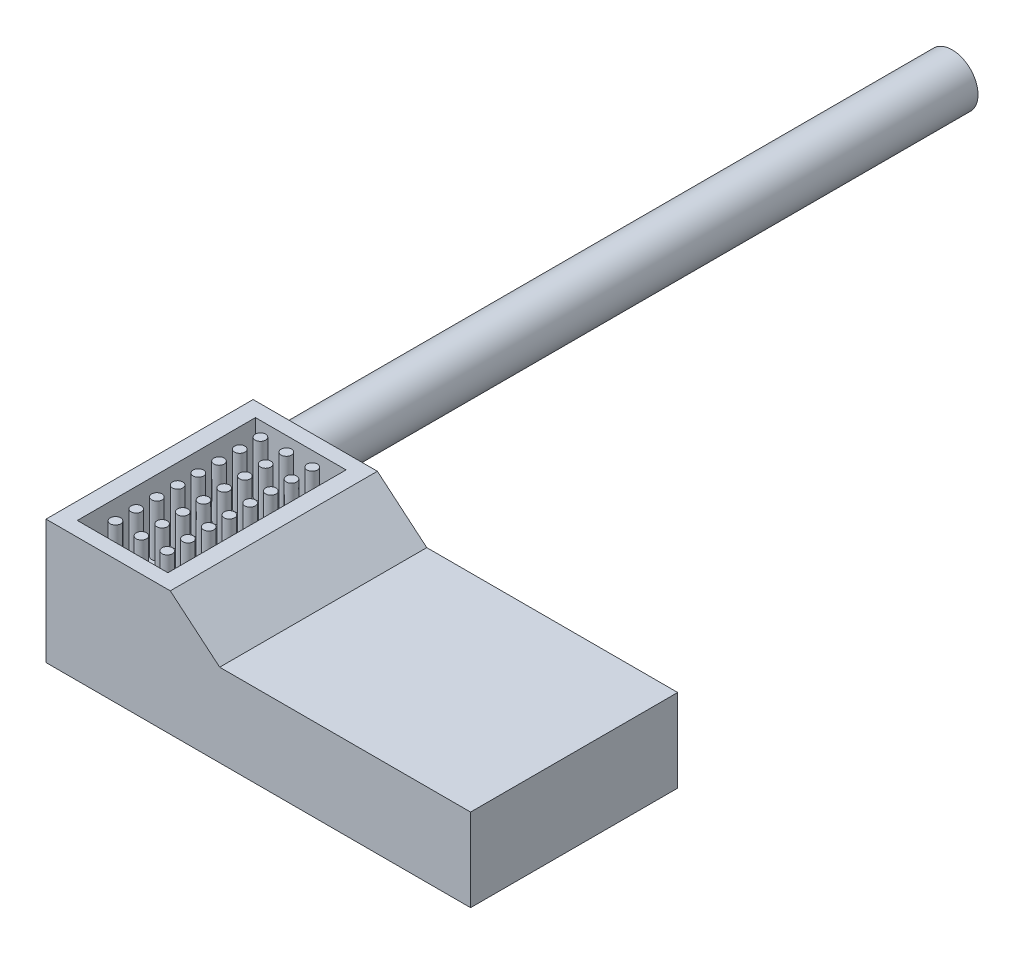
SolidWorks part; units mm, degrees
ref_plane "Front Plane" through (0, 0, 0) normal (0, 0, 1) x (1, 0, 0)
ref_plane "Top Plane" through (0, 0, 0) normal (0, 1, 0) x (1, 0, 0)
ref_plane "Right Plane" through (0, 0, 0) normal (1, 0, 0) x (0, 0, -1)
sketch "Sketch2" plane through (0, 0, 0) normal (0, 0, 1) x (1, 0, 0)
  line L0 (-3.6523, 7.7816) -> (-8.4239, 11.7816)
  line L1 (20.5761, -0.2184) -> (-20.4239, -0.2184)
  line L2 (20.5761, -0.2184) -> (20.5761, 7.7816)
  line L3 (20.5761, 7.7816) -> (-3.6523, 7.7816)
  line L4 (-20.4239, 11.7816) -> (-20.4239, -0.2184)
  line L7 (-8.4239, 11.7816) -> (-20.4239, 11.7816)
  point P0 (0, 0)
  dimension "D1" = 41
  dimension "D2" = 12
  dimension "D3" = 12
  dimension "D4" = 8
extrude "Boss-Extrude1" add sketch "Sketch2" along normal blind 10 and the other way blind 10
sketch "Sketch4" plane through (0, 11.7816, 0) normal (0, 1, 0) x (1, 0, 0)
  line L0 (-14.4239, 10) -> (-14.4239, -10) construction
  line L1 (-8.4239, 10) -> (-20.4239, 10) construction
  line L2 (-8.4239, -10) -> (-20.4239, -10) construction
  line L3 (-20.4239, 0) -> (-8.4239, 0) construction
  line L4 (-20.4239, 10) -> (-20.4239, -10) construction
  line L5 (-8.4239, 10) -> (-8.4239, -10) construction
  line L7 (-10.0498, -8.6025) -> (-18.7979, -8.6025)
  line L8 (-10.0498, -8.6025) -> (-10.0498, 8.6025)
  line L9 (-10.0498, 8.6025) -> (-18.7979, 8.6025)
  line L10 (-18.7979, -8.6025) -> (-18.7979, 8.6025)
  line L11 (-10.0498, -8.6025) -> (-18.7979, 8.6025) construction
  line L12 (-10.0498, 8.6025) -> (-18.7979, -8.6025) construction
  point P12 (-14.4239, 0)
extrude "Cut-Extrude1" cut sketch "Sketch4" against normal blind 5
sketch "Sketch5" plane through (0, 6.7816, 0) normal (0, 1, 0) x (1, 0, 0)
  line L0 (-18.7979, 7.2092) -> (-10.0498, 7.2092) construction
  line L1 (-18.7979, 8.6025) -> (-18.7979, -8.6025) construction
  line L2 (-10.0498, -8.6025) -> (-10.0498, 8.6025) construction
  circle A0 centre (-16.9239, 7.2092) radius 0.5
  circle A1 centre (-14.4239, 7.2092) radius 0.5
  circle A2 centre (-11.9239, 7.2092) radius 0.5
  circle A3 centre (-16.9239, 5.2092) radius 0.5
  circle A4 centre (-11.9239, 5.2092) radius 0.5
  circle A5 centre (-14.4239, 5.2092) radius 0.5
  circle A6 centre (-16.9239, 3.2092) radius 0.5
  circle A7 centre (-11.9239, 3.2092) radius 0.5
  circle A8 centre (-14.4239, 3.2092) radius 0.5
  circle A9 centre (-16.9239, 1.2092) radius 0.5
  circle A10 centre (-11.9239, 1.2092) radius 0.5
  circle A11 centre (-14.4239, 1.2092) radius 0.5
  circle A12 centre (-16.9239, -0.7908) radius 0.5
  circle A13 centre (-11.9239, -0.7908) radius 0.5
  circle A14 centre (-14.4239, -0.7908) radius 0.5
  circle A15 centre (-16.9239, -2.7908) radius 0.5
  circle A16 centre (-11.9239, -2.7908) radius 0.5
  circle A17 centre (-14.4239, -2.7908) radius 0.5
  circle A18 centre (-16.9239, -4.7908) radius 0.5
  circle A19 centre (-11.9239, -4.7908) radius 0.5
  circle A20 centre (-14.4239, -4.7908) radius 0.5
  circle A21 centre (-16.9239, -6.7908) radius 0.5
  circle A22 centre (-11.9239, -6.7908) radius 0.5
  circle A23 centre (-14.4239, -6.7908) radius 0.5
  dimension "D1" = 1
  dimension "D2" = 1
  dimension "D3" = 1
  dimension "D4" = 2.5
  dimension "D5" = 2.5
  dimension "D6" = 8
extrude "Boss-Extrude2" add sketch "Sketch5" along normal blind 5
sketch "Sketch6" plane through (0, 0, 0) normal (0, 0, 1) x (1, 0, 0)
  line L0 (-20.4239, -0.2184) -> (-26.3015, -0.2184) construction
  line L2 (-20.4239, 11.7816) -> (-20.4239, -0.2184) construction
  circle A0 centre (-22.9239, 2.2816) radius 2.5
  dimension "D1" = 5
extrude "Boss-Extrude3" add sketch "Sketch6" against normal blind 80 separate body
